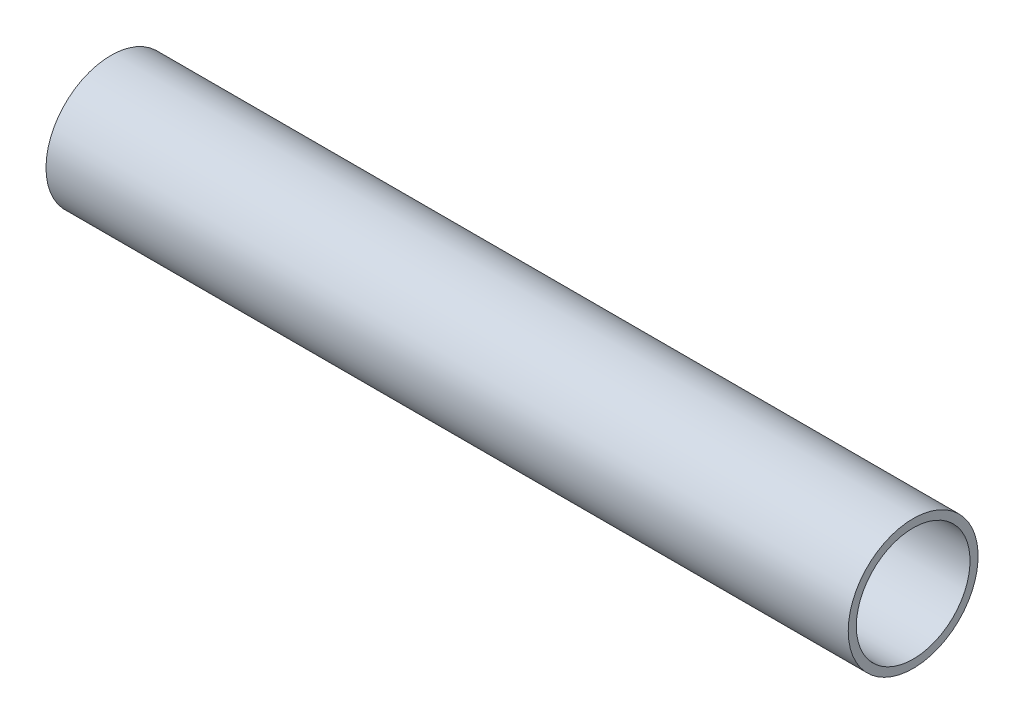
SolidWorks part; units mm, degrees
material "PE High Density"
ref_plane "Front Plane" through (0, 0, 0) normal (0, 0, 1) x (1, 0, 0)
ref_plane "Top Plane" through (0, 0, 0) normal (0, 1, 0) x (1, 0, 0)
ref_plane "Right Plane" through (0, 0, 0) normal (1, 0, 0) x (0, 0, -1)
sketch "Sketch2" plane through (0, 0, 0) normal (0, 0, 1) x (1, 0, 0)
  line L0 (0, 0) -> (74.8146, 0) construction
  line L2 (0, 141.732) -> (2000, 141.732)
  line L3 (0, 141.732) -> (0, 161.925)
  line L4 (0, 161.925) -> (2000, 161.925)
  line L5 (2000, 141.732) -> (2000, 161.925)
  dimension "D1" = 141.732
  dimension "D3" = 2000
  dimension "D2" = 161.925
revolve "Revolve1" add sketch "Sketch2" angle 360 about L0
ref_plane "Midplane" through (1000, 0, 0) normal (-1, 0, 0) x (0, 0, 1)
equation "\"ID\"= 11.160in"
equation "\"OD\"= 12.75in"
equation "\"Length\"= 2m"
equation "\"D1@Sketch2\"=\"ID\"/2"
equation "\"D3@Sketch2\"=\"Length\""
equation "\"D2@Sketch2\"=\"OD\"/2"
